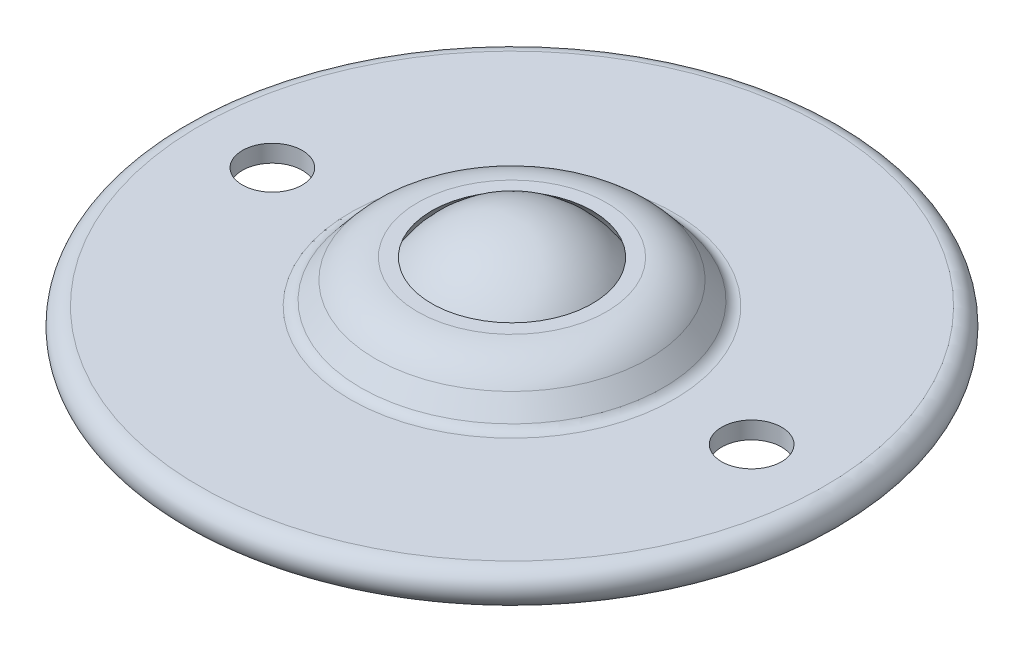
SolidWorks part; units mm, degrees
ref_plane "Front" through (0, 0, 0) normal (0, 0, 1) x (1, 0, 0)
ref_plane "Top" through (0, 0, 0) normal (0, 1, 0) x (1, 0, 0)
ref_plane "Right" through (0, 0, 0) normal (1, 0, 0) x (0, 0, -1)
sketch "Sketch1" plane through (0, 0, 0) normal (0, 0, 1) x (1, 0, 0)
  line L0 (14.4146, 2.4063) -> (28.9594, 2.4063)
  line L1 (15.0813, -0.7938) -> (28.9594, -0.7938)
  line L2 (7.4539, 6.33) -> (11.1448, 6.33)
  line L3 (11.1448, 6.33) -> (14.4146, 2.4063)
  line L4 (30.5594, 0.8063) -> (-30.5594, 0.8063) construction
  line L5 (14.4146, 2.4063) -> (-14.4146, 2.4063) construction
  line L6 (0, -12.7) -> (0, -9.779)
  line L7 (15.0813, -0.7938) -> (-15.0813, -0.7938) construction
  line L8 (14.4146, 2.4063) -> (15.7479, 0.8063) construction
  line L9 (28.9594, -0.7938) -> (-28.9594, -0.7938) construction
  circle A0 centre (0, 0) radius 9.525 construction
  arc A1 (28.9594, 2.4063) -> (28.9594, -0.7938) centre (28.9594, 0.8063) cw
  arc A4 (0, -9.779) -> (7.4539, 6.33) centre (0, 0) ccw
  arc A5 (0, -12.7) -> (15.0813, -0.7938) centre (0, 2.8046) ccw
  circle A8 centre (0, 0) radius 9.779 construction
  point P5 (15.0812, 1.6063)
  point P16 (0, 0.8063)
  point P17 (0, 2.4062)
  point P25 (12.954, 0)
  point P29 (0, -0.7937)
  dimension "D1" = 50.195
  dimension "Ball Dia" = 19.05
  dimension "D2" = 0.254
  dimension "Thickness" = 3.2
  dimension "Body Ht" = 6.33
  dimension "Flange Lg" = 61.1187
  dimension "C Bottom Ht" = 11.9062
  dimension "B Bottom Dia" = 30.1625
  dimension "A Top Ht" = 10.3187
revolve "Revolve1" add sketch "Sketch1" angle 360 mid plane about L6
sketch "Sketch2" plane through (0, 0, 0) normal (0, 0, 1) x (1, 0, 0)
  line L0 (0, 9.525) -> (0, -9.525)
  circle A0 centre (0, 0) radius 9.525 construction
  arc A1 (0, -9.525) -> (0, 9.525) centre (0, 0) ccw
revolve "Revolve2" add sketch "Sketch2" angle 360 mid plane about L0
sketch "Sketch3" plane through (0, 2.4063, 0) normal (0, 1, 0) x (1, 0, 0)
  circle A0 centre (-22.225, 0) radius 2.7781
  circle A1 centre (22.225, 0) radius 2.7781
  circle A2 centre (0, 0) radius 22.225 construction
  dimension "Bolt Hole Dia" = 5.5562
  dimension "Hole Spacing" = 44.45
extrude "Cut-Extrude1" cut sketch "Sketch3" against normal through all
sketch "Sketch4" [suppressed] plane through (0, 0, 0) normal (0, 0, 1) x (1, 0, 0)
  line L0 (11.4698, 2.4125) -> (10.5636, 3.5) construction
  line L1 (13.1364, 0.4125) -> (10.5636, 3.5)
  line L2 (13.1364, 0.4125) -> (19.4313, 0.4125)
  line L3 (19.4313, 0.4125) -> (19.4313, 2.4125)
  line L4 (19.4313, 2.4125) -> (-19.4313, 2.4125) construction
  line L5 (10.5636, 3.5) -> (19.4313, 2.4125)
  line L6 (21.4312, 0.4125) -> (-21.4312, 0.4125) construction
revolve "Cut-Revolve1" [suppressed] cut sketch "Sketch4" angle 360 mid plane
fillet "Fillet1" [suppressed] radius 6.35
fillet "Fillet2" [suppressed] radius 0.508
fillet "Fillet3" [suppressed] radius 0.508
sketch "Sketch5" plane through (0, 0, 0) normal (0, 0, 1) x (1, 0, 0)
  line L0 (15.3753, 0.8063) -> (28.9594, 0.8063)
  line L1 (28.9594, 0.8063) -> (28.9594, -0.7938)
  line L2 (30.5594, 0.8063) -> (-30.5594, 0.8063) construction
  line L3 (15.0813, -0.7937) -> (28.9594, -0.7938) construction
  line L4 (15.0813, -0.7937) -> (28.9594, -0.7938)
  arc A0 (-15.0813, -0.7938) -> (15.0813, -0.7937) centre (0, 2.8046) ccw construction
  arc A1 (15.0813, -0.7937) -> (15.3753, 0.8063) centre (0, 2.8046) ccw
revolve "Cut revolve" cut sketch "Sketch5" angle 360 mid plane
fillet "Fillet4" radius 5.08 1 edges at (0, 6.33, -11.1448)
fillet "Fillet5" radius 1.27 2 edges at (0, 2.4063, -14.4146) (0, 0.8063, 15.3753)
